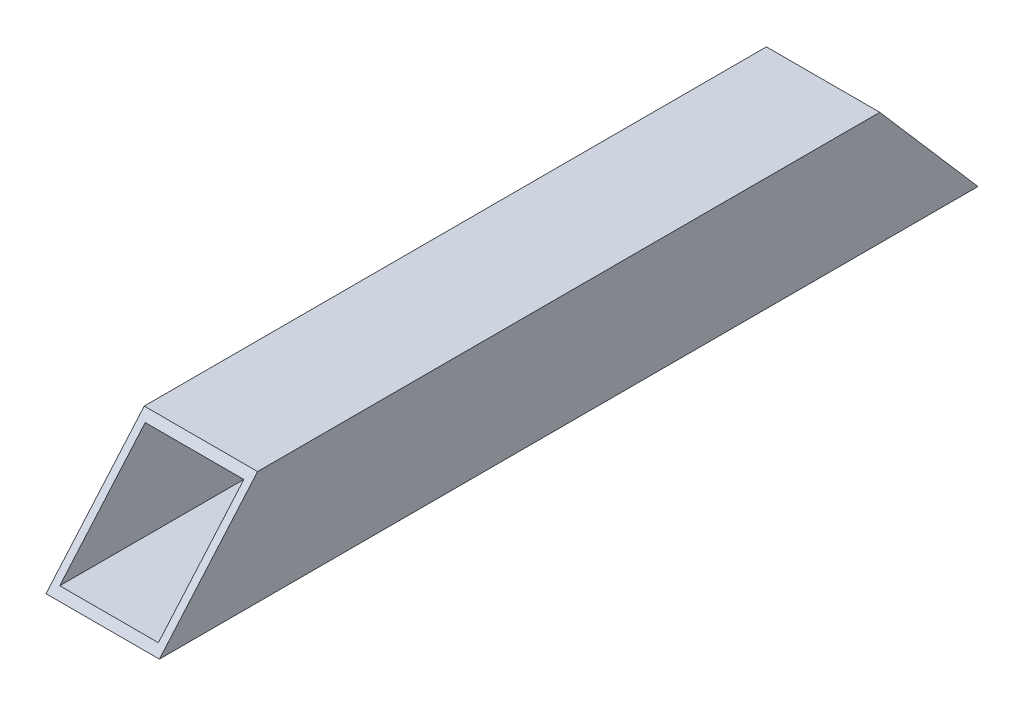
SolidWorks part; units mm, degrees
ref_plane "Front Plane" through (0, 0, 0) normal (0, 0, 1) x (1, 0, 0)
ref_plane "Top Plane" through (0, 0, 0) normal (0, 1, 0) x (1, 0, 0)
ref_plane "Right Plane" through (0, 0, 0) normal (1, 0, 0) x (0, 0, -1)
sketch "Sketch1" plane through (0, 0, 0) normal (0, 0, 1) x (1, 0, 0)
  line L1 (0, 0) -> (25.4, 0)
  line L2 (0, 0) -> (0, 25.4)
  line L3 (0, 25.4) -> (25.4, 25.4)
  line L4 (25.4, 0) -> (25.4, 25.4)
  dimension "D1" = 25.4
  dimension "D2" = 25.4
extrude "Boss-Extrude1" add sketch "Sketch1" along normal blind 183.4
sketch "Sketch2" plane through (25.4, 0, 0) normal (1, 0, 0) x (0, 0, -1)
  line L0 (-183.4, 0) -> (-161.3956, 25.4)
  line L1 (-183.4, 25.4) -> (0, 25.4) construction
  line L2 (-161.3956, 25.4) -> (-183.4, 25.4)
  line L3 (-183.4, 25.4) -> (-183.4, 0)
  line L4 (-183.4, 0) -> (0, 0) construction
  dimension "D1" = 49.097
extrude "Cut-Extrude1" cut sketch "Sketch2" against normal blind 224.6
sketch "Sketch3" plane through (25.4, 0, 0) normal (1, 0, 0) x (0, 0, -1)
  line L0 (0, 0) -> (-22.0044, 25.4)
  line L1 (-161.3956, 25.4) -> (0, 25.4) construction
  line L2 (-22.0044, 25.4) -> (0, 25.4)
  line L3 (0, 0) -> (0, 25.4) construction
  line L4 (0, 25.4) -> (0, 0)
  line L5 (-183.4, 0) -> (0, 0) construction
  dimension "D1" = 49.097
extrude "Cut-Extrude2" cut sketch "Sketch3" against normal blind 224.6
shell "Shell1" thickness 1.651 removed face at (12.7, 12.7, 172.3978) removed face at (12.7, 12.7, 11.0022)
equation "\"D1@Sketch2\"=(180-atn(250/36))/2"
equation "\"D1@Sketch3\"=(180-atn(250/36))/2"
equation "\"ExtrusionLen\"= 183.40"
equation "\"D1@Boss-Extrude1\"=\"ExtrusionLen\""
